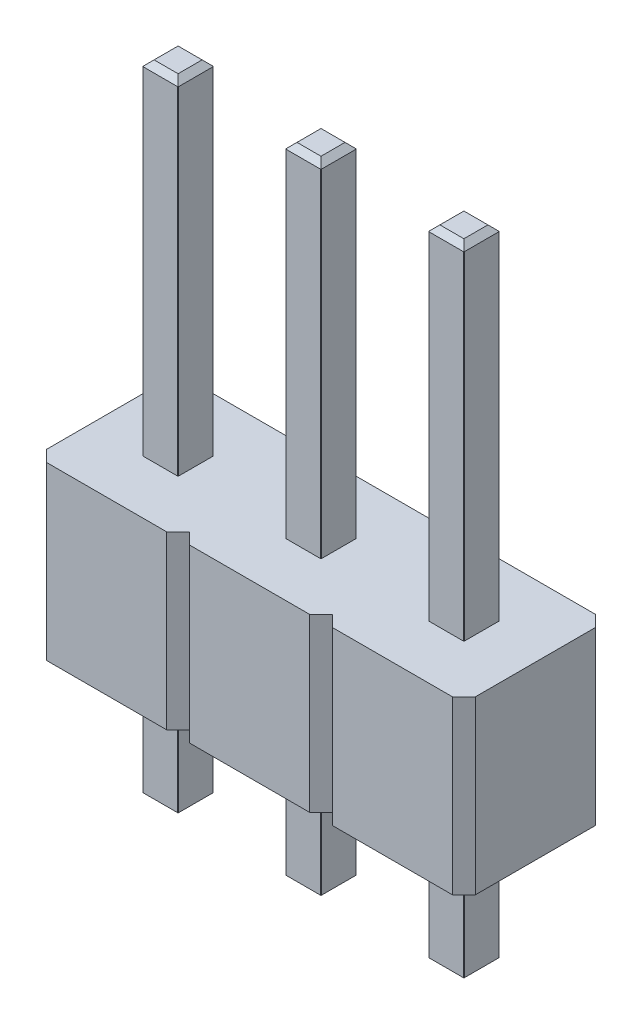
SolidWorks part; units mm, degrees
ref_plane "Front Plane" through (0, 0, 0) normal (0, 0, 1) x (1, 0, 0)
ref_plane "Top Plane" through (0, 0, 0) normal (0, 1, 0) x (1, 0, 0)
ref_plane "Right Plane" through (0, 0, 0) normal (1, 0, 0) x (0, 0, -1)
sketch "Sketch2" plane through (0, 0, 0) normal (0, 1, 0) x (1, 0, 0)
  line L0 (-1.25, -1.05) -> (-1.05, -1.25)
  line L1 (-1.05, 1.25) -> (1.05, 1.25)
  line L2 (-1.25, 1.05) -> (-1.25, -1.05) construction
  line L3 (-1.05, -1.25) -> (1.05, -1.25)
  line L4 (1.25, 1.05) -> (1.25, -1.05) construction
  line L5 (1.05, -1.25) -> (1.25, -1.05)
  line L6 (1.05, 1.25) -> (1.25, 1.05)
  line L7 (-1.25, 1.05) -> (-1.05, 1.25)
  line L8 (-1.25, -1.05) -> (-1.45, -1.25)
  line L9 (-1.45, -1.25) -> (-3.55, -1.25)
  line L10 (-3.55, -1.25) -> (-3.75, -1.05)
  line L11 (-3.55, 1.25) -> (-3.75, 1.05)
  line L12 (-1.45, 1.25) -> (-3.55, 1.25)
  line L13 (-1.25, 1.05) -> (-1.45, 1.25)
  line L14 (3.75, -1.05) -> (3.55, -1.25)
  line L15 (3.55, -1.25) -> (1.45, -1.25)
  line L16 (1.45, -1.25) -> (1.25, -1.05)
  line L17 (1.45, 1.25) -> (1.25, 1.05)
  line L18 (3.55, 1.25) -> (1.45, 1.25)
  line L19 (3.75, 1.05) -> (3.55, 1.25)
  line L20 (3.75, -1.05) -> (3.75, 1.05)
  line L21 (-3.75, -1.05) -> (-3.75, 1.05)
  point P0 (-1.25, 1.25)
  point P1 (1.25, -1.25)
  point P2 (-1.25, -1.25)
  point P3 (1.25, 1.25)
  dimension "D1" = 2.5
  dimension "D2" = 1.25
  dimension "D3" = 2.5
  dimension "D4" = 1.25
extrude "Boss-Extrude1" add sketch "Sketch2" along normal blind 3
sketch "Sketch3" plane through (0, 3, 0) normal (0, 1, 0) x (1, 0, 0)
  line L0 (-1.25, 1.05) -> (-1.25, -1.05) construction
  line L1 (0.3, 0.31) -> (-0.3, 0.31)
  line L2 (0.31, 0.3) -> (0.31, -0.3)
  line L3 (0.3, -0.31) -> (-0.3, -0.31)
  line L4 (-0.31, 0.3) -> (-0.31, -0.3)
  line L5 (0.31, 0.31) -> (-0.31, -0.31) construction
  line L6 (0.31, -0.31) -> (-0.31, 0.31) construction
  line L7 (1.25, -1.05) -> (1.25, 1.05) construction
  line L8 (-0.3, 0.31) -> (-0.31, 0.3)
  line L9 (0.31, 0.3) -> (0.3, 0.31)
  line L10 (0.31, -0.3) -> (0.3, -0.31)
  line L11 (-0.3, -0.31) -> (-0.31, -0.3)
  line L12 (-2.81, -0.31) -> (-2.19, 0.31) construction
  line L13 (-2.81, 0.31) -> (-2.19, -0.31) construction
  line L14 (-2.2, -0.31) -> (-2.19, -0.3)
  line L15 (-2.81, -0.3) -> (-2.8, -0.31)
  line L16 (-2.81, 0.3) -> (-2.8, 0.31)
  line L17 (-2.2, 0.31) -> (-2.19, 0.3)
  line L18 (-2.19, 0.3) -> (-2.19, -0.3)
  line L19 (-2.8, -0.31) -> (-2.2, -0.31)
  line L20 (-2.81, 0.3) -> (-2.81, -0.3)
  line L21 (-2.8, 0.31) -> (-2.2, 0.31)
  line L22 (2.19, -0.31) -> (2.81, 0.31) construction
  line L23 (2.19, 0.31) -> (2.81, -0.31) construction
  line L24 (2.8, -0.31) -> (2.81, -0.3)
  line L25 (2.19, -0.3) -> (2.2, -0.31)
  line L26 (2.19, 0.3) -> (2.2, 0.31)
  line L27 (2.8, 0.31) -> (2.81, 0.3)
  line L28 (2.81, 0.3) -> (2.81, -0.3)
  line L29 (2.2, -0.31) -> (2.8, -0.31)
  line L30 (2.19, 0.3) -> (2.19, -0.3)
  line L31 (2.2, 0.31) -> (2.8, 0.31)
  point P0 (0, 0)
  point P34 (-2.5, 0)
  point P47 (2.5, 0)
  dimension "D1" = 0.62
  dimension "D2" = 0.62
extrude "Boss-Extrude2" add sketch "Sketch3" along normal blind 6 and the other way blind 5.2
chamfer "Chamfer1" distance 0.1 angle 45 24 edges at (-2.81, 9, 0) (-2.5, 9, -0.31) (-2.19, 9, 0) (-2.5, 9, 0.31) (2.81, -2.2, 0) (2.5, -2.2, -0.31) (2.19, -2.2, 0) (2.5, -2.2, 0.31) (-0.31, -2.2, 0) (0, -2.2, 0.31) (0.31, -2.2, 0) (0, -2.2, -0.31) (-2.19, -2.2, 0) (-2.5, -2.2, -0.31) (-2.81, -2.2, 0) (-2.5, -2.2, 0.31) (2.19, 9, 0) (2.5, 9, -0.31) (2.81, 9, 0) (2.5, 9, 0.31) (0, 9, -0.31) (0.31, 9, 0) (0, 9, 0.31) (-0.31, 9, 0)
